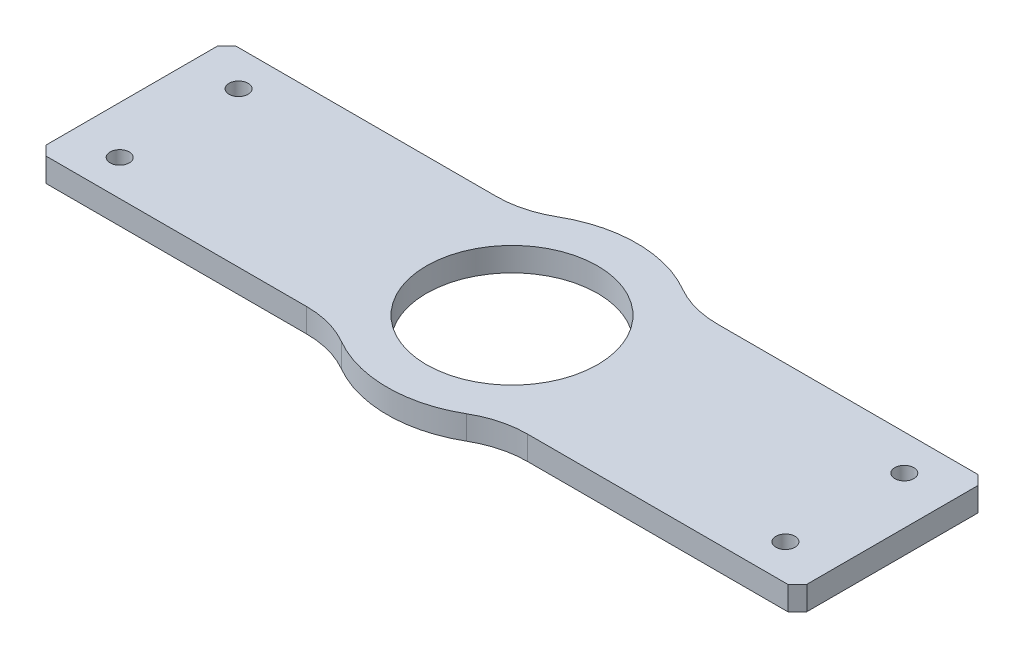
SolidWorks part; units mm, degrees
material "6061-T6 (SS)"
ref_plane "Front" through (0, 0, 0) normal (0, 0, 1) x (1, 0, 0)
ref_plane "Top" through (0, 0, 0) normal (0, 1, 0) x (1, 0, 0)
ref_plane "Right" through (0, 0, 0) normal (1, 0, 0) x (0, 0, -1)
sketch "Sketch1" plane through (0, 0, 0) normal (0, 1, 0) x (1, 0, 0)
  line L0 (203.2, 0) -> (203.2, 19.05) construction
  line L1 (0, 0) -> (72.1135, 0)
  line L2 (0, 0) -> (0, 50.8)
  line L3 (0, 50.8) -> (72.1135, 50.8)
  line L4 (203.2, 0) -> (203.2, 50.8)
  line L5 (0, 50.8) -> (203.2, 0) construction
  line L6 (131.0865, 50.8) -> (203.2, 50.8)
  line L7 (131.0865, 0) -> (203.2, 0)
  arc A0 (84.8644, -3.4324) -> (118.3356, -3.4324) centre (101.6, 25.4) ccw
  arc A1 (118.3356, 54.2324) -> (84.8644, 54.2324) centre (101.6, 25.4) ccw
  arc A2 (72.1135, 0) -> (84.8644, -3.4324) centre (72.1135, -25.4) cw
  arc A3 (131.0865, 0) -> (118.3356, -3.4324) centre (131.0865, -25.4) ccw
  arc A4 (131.0865, 50.8) -> (118.3356, 54.2324) centre (131.0865, 76.2) cw
  arc A5 (72.1135, 50.8) -> (84.8644, 54.2324) centre (72.1135, 76.2) ccw
  point P18 (123.1923, 50.8)
  dimension "D2" = 66.675
  dimension "D3" = 25.4
  dimension "D1" = 50.8
extrude "Boss-Extrude1" add sketch "Sketch1" along normal blind 6.35
sketch "Sketch4" plane through (0, 6.35, 0) normal (0, 1, 0) x (1, 0, 0)
  line L0 (0, 0) -> (12.7, 9.525) construction
  line L1 (0, 0) -> (72.1135, 0) construction
  line L6 (12.7, 9.525) -> (12.7, 41.275) construction
  line L7 (12.7, 41.275) -> (25.4, 50.8) construction
  line L8 (72.1135, 50.8) -> (0, 50.8) construction
  line L9 (101.6, 0) -> (101.6, 25.4) construction
  arc A0 (84.8644, -3.4324) -> (118.3356, -3.4324) centre (101.6, 25.4) ccw construction
  point P0 (12.7, 41.275)
  point P4 (12.7, 9.525)
  point P34 (190.5, 9.525)
  point P36 (190.5, 41.275)
  dimension "D1" = 31.75
  dimension "D2" = 25.4
hole_wizard "#10 Clearance Hole1" positions "Sketch4" profile "Sketch3" hole size "#10" standard "ANSI Inch" end condition up to next
sketch "Sketch3" plane through (12.7, 6.35, -41.275) normal (1, 0, 0) x (0, 0, 1)
  line L0 (0, 0) -> (0, 6.35)
  line L1 (0, 6.35) -> (2.5527, 6.35)
  line L2 (2.5527, 6.35) -> (2.5527, 0)
  line L5 (2.5527, 0) -> (0, 0)
  line L11 (0, -6.35) -> (0, 107.95) construction
  dimension "Thru Hole Dia." = 5.1054
  dimension "Thru Hole Depth" = 6.35
sketch "Sketch5" plane through (0, 6.35, 0) normal (0, 1, 0) x (1, 0, 0)
  circle A0 centre (101.6, 25.4) radius 22.86
  arc A1 (118.3356, 54.2324) -> (84.8644, 54.2324) centre (101.6, 25.4) ccw construction
  dimension "D1" = 45.72
extrude "Cut-Extrude1" cut sketch "Sketch5" against normal through all
chamfer "Chamfer1" distance 2.54 angle 45 4 edges at (0, 3.175, -50.8) (203.2, 3.175, -50.8) (203.2, 3.175, 0) (0, 3.175, 0)
